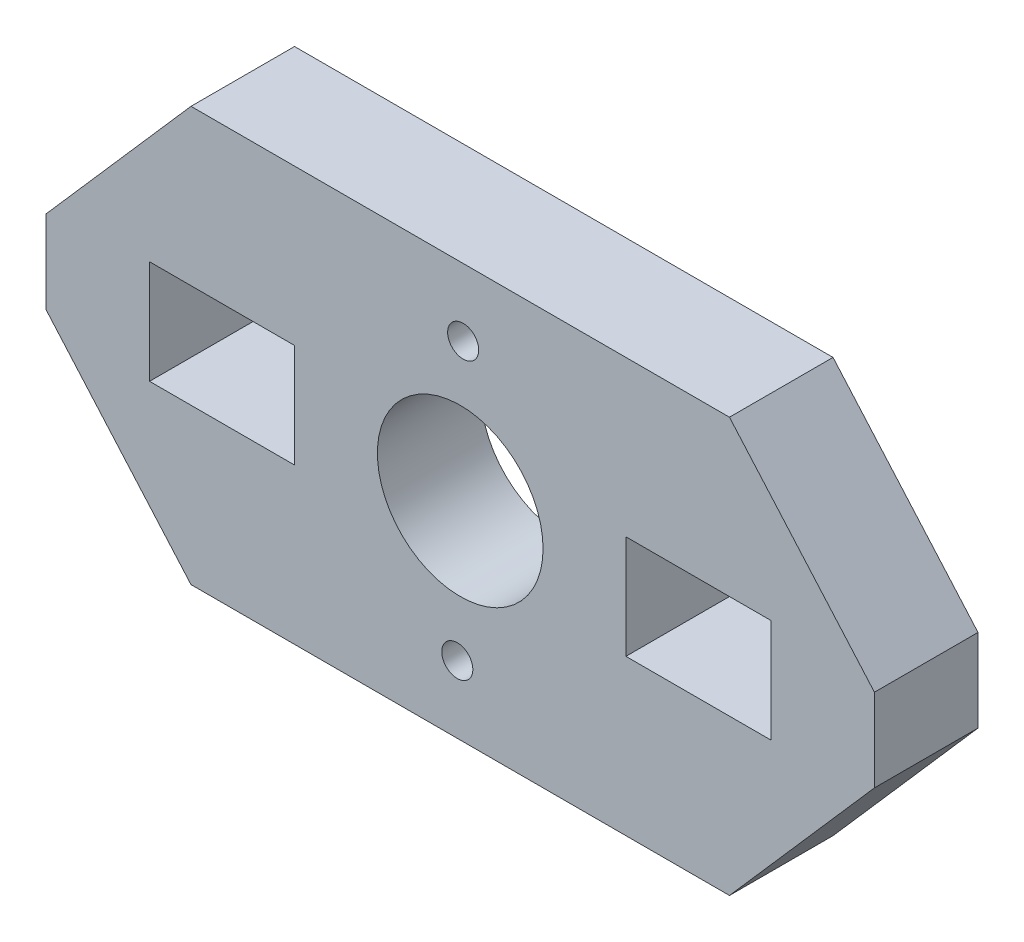
SolidWorks part; units mm, degrees
material "Acrylic (Medium-high impact)"
ref_plane "Front Plane" through (0, 0, 0) normal (0, 0, 1) x (1, 0, 0)
ref_plane "Top Plane" through (0, 0, 0) normal (0, 1, 0) x (1, 0, 0)
ref_plane "Right Plane" through (0, 0, 0) normal (1, 0, 0) x (0, 0, -1)
sketch "Sketch1" plane through (0, 0, 0) normal (0, 0, 1) x (1, 0, 0)
  line L0 (2.2286, -8.8071) -> (-37.7714, -8.8071) construction
  line L1 (-30.7714, -18.8071) -> (-4.7714, -18.8071)
  line L3 (-30.7714, 1.1929) -> (-4.7714, 1.1929)
  line L8 (-4.7714, 1.1929) -> (2.2286, -6.8071)
  line L9 (2.2286, -10.8071) -> (-4.7714, -18.8071)
  line L10 (-17.7714, 1.1929) -> (-17.7714, -18.8071) construction
  line L13 (-30.7714, 1.1929) -> (-37.7714, -6.8071)
  line L15 (-37.7714, -10.8071) -> (-30.7714, -18.8071)
  line L16 (-37.7714, -6.8071) -> (-37.7714, -10.8071)
  line L17 (2.2286, -6.8071) -> (2.2286, -10.8071)
  circle A0 centre (-17.7714, -8.8071) radius 4
  circle A1 centre (-17.6297, -2.0586) radius 0.75
  circle A2 centre (-17.9131, -15.5557) radius 0.75
  dimension "D2" = 8
  dimension "D1" = 20
  dimension "D3" = 2
  dimension "D4" = 2
  dimension "D5" = 7
  dimension "D6" = 7
  dimension "D8" = 2
  dimension "D9" = 2
extrude "Boss-Extrude1" add sketch "Sketch1" along normal blind 5
sketch "Sketch2" plane through (0, 0, 5) normal (0, 0, 1) x (1, 0, 0)
  line L0 (-32.7714, -1.0929) -> (-32.7714, -16.5214) construction
  line L1 (-30.7714, 1.1929) -> (-37.7714, -6.8071) construction
  line L2 (-37.7714, -10.8071) -> (-30.7714, -18.8071) construction
  line L3 (-37.7714, -6.8071) -> (-37.7714, -10.8071) construction
  line L4 (-37.7714, -8.8071) -> (2.2286, -8.8071)
  line L5 (2.2286, -10.8071) -> (2.2286, -6.8071) construction
  line L6 (-17.7714, 1.1929) -> (-17.7714, -18.8071) construction
  line L7 (-32.7714, -6.3071) -> (-25.7714, -6.3071)
  line L8 (-32.7714, -6.3071) -> (-32.7714, -11.3071)
  line L9 (-32.7714, -11.3071) -> (-25.7714, -11.3071)
  line L10 (-25.7714, -6.3071) -> (-25.7714, -11.3071)
  line L11 (-4.7714, 1.1929) -> (-30.7714, 1.1929) construction
  line L12 (-30.7714, -18.8071) -> (-4.7714, -18.8071) construction
  line L13 (-2.7714, -11.3071) -> (-9.7714, -11.3071)
  line L14 (-9.7714, -6.3071) -> (-9.7714, -11.3071)
  line L15 (-2.7714, -6.3071) -> (-9.7714, -6.3071)
  line L16 (-2.7714, -6.3071) -> (-2.7714, -11.3071)
  dimension "D1" = 5
  dimension "D2" = 5
  dimension "D3" = 7
  dimension "D4" = 2.5
extrude "Cut-Extrude1" cut sketch "Sketch2" against normal blind 5 and the other way blind 5 contours L10 L7 L8 L4 | L10 L4 L8 L9 | L16 L15 L14 L4 | L16 L4 L14 L13 region at (-29.2714, -7.5571, 5) region at (-6.2714, -7.5571, 5) region at (-6.2714, -10.0571, 5) region at (-29.2714, -10.0571, 5)
